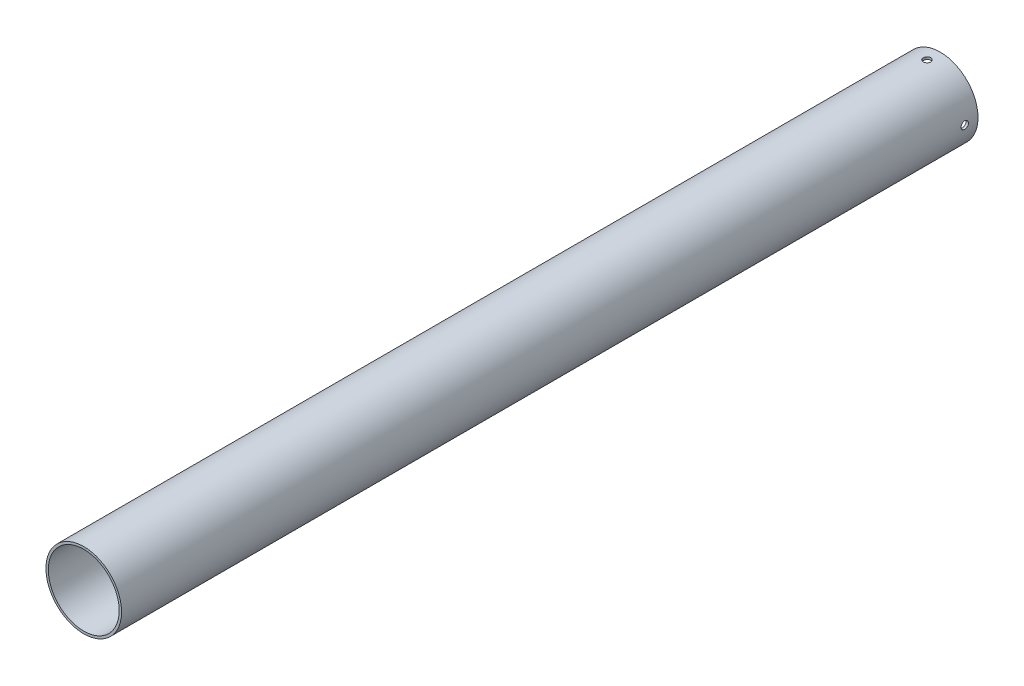
SolidWorks part; units mm, degrees
material "PC High Viscosity"
ref_plane "Front Plane" through (0, 0, 0) normal (0, 0, 1) x (1, 0, 0)
ref_plane "Top Plane" through (0, 0, 0) normal (0, 1, 0) x (1, 0, 0)
ref_plane "Right Plane" through (0, 0, 0) normal (1, 0, 0) x (0, 0, -1)
sketch "Sketch1" plane through (0, 0, 0) normal (0, 0, 1) x (1, 0, 0)
  circle A0 centre (0, 0) radius 23.8125
  circle A1 centre (0, 0) radius 25.4
  dimension "D1" = 50.8
  dimension "D2" = 47.625
extrude "Boss-Extrude1" add sketch "Sketch1" along normal mid plane 575.213
sketch "Sketch2" plane through (0, 0, 0) normal (1, 0, 0) x (0, 0, -1)
  line L0 (287.6065, -25.4) -> (287.6065, 25.4) construction
  circle A0 centre (278.7165, 0) radius 2.4892
  point P2 (0, 0)
  dimension "D1" = 8.89
  dimension "D2" = 4.9784
extrude "Cut-Extrude1" cut sketch "Sketch2" against normal through all both and the other way through all
sketch "Sketch3" plane through (0, 0, 0) normal (0, 1, 0) x (1, 0, 0)
  line L0 (25.4, 287.6065) -> (-25.4, 287.6065) construction
  circle A0 centre (0, 278.7165) radius 2.4892
  point P2 (0, 0)
  point P4 (0, 269.254)
  dimension "D1" = 4.9784
  dimension "D2" = 8.89
extrude "Cut-Extrude2" cut sketch "Sketch3" against normal through all both and the other way through all
equation "\"D1@Boss-Extrude1\"=21.125in+3.625mm"
